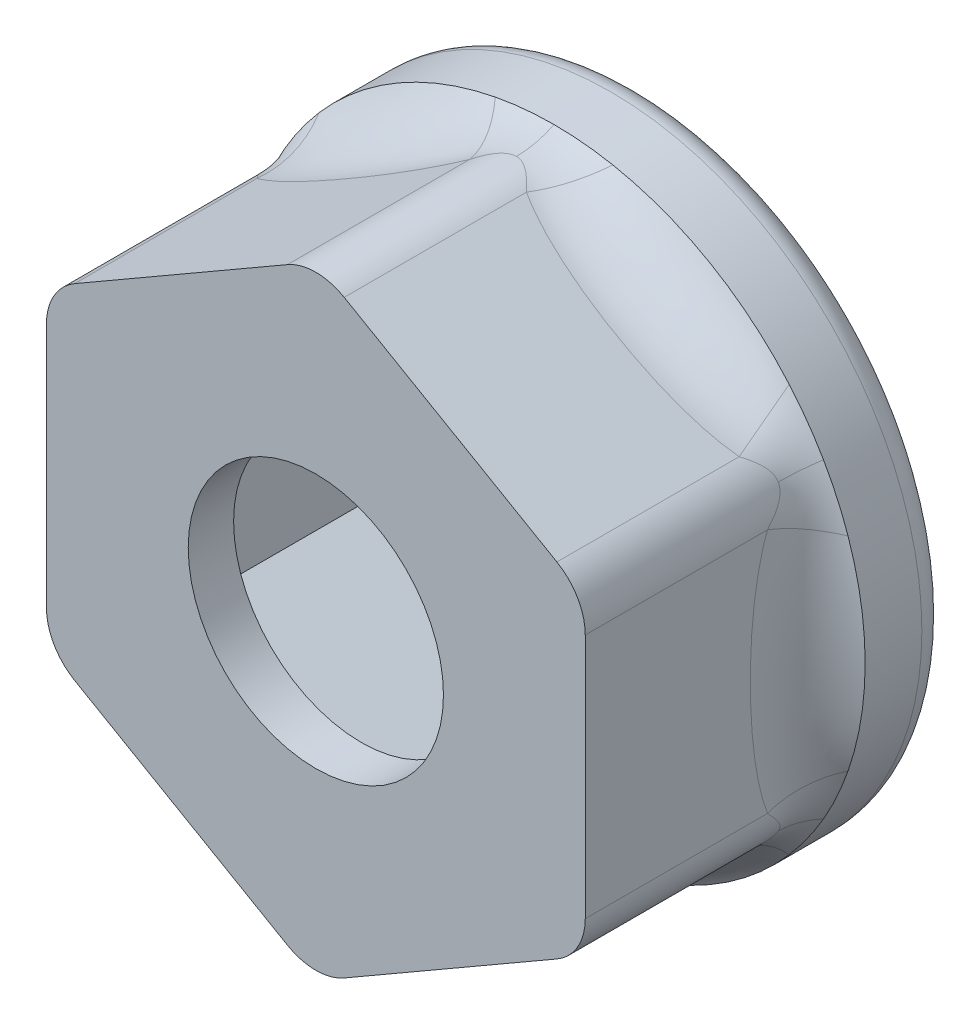
SolidWorks part; units mm, degrees
ref_plane "Front Plane" through (0, 0, 0) normal (0, 0, 1) x (1, 0, 0)
ref_plane "Top Plane" through (0, 0, 0) normal (0, 1, 0) x (1, 0, 0)
ref_plane "Right Plane" through (0, 0, 0) normal (1, 0, 0) x (0, 0, -1)
sketch "Sketch1" plane through (0, 0, 0) normal (0, 0, 1) x (1, 0, 0)
  line L1 (0, -7.5633) -> (6.55, -3.7816)
  line L2 (6.55, -3.7816) -> (6.55, 3.7816)
  line L3 (6.55, 3.7816) -> (0, 7.5633)
  line L4 (0, 7.5633) -> (-6.55, 3.7816)
  line L5 (-6.55, 3.7816) -> (-6.55, -3.7816)
  line L6 (-6.55, -3.7816) -> (0, -7.5633)
  line L7 (0, -10.9697) -> (9.5, -5.4848) construction
  line L8 (9.5, -5.4848) -> (9.5, 5.4848) construction
  line L9 (9.5, 5.4848) -> (0, 10.9697) construction
  line L10 (0, 10.9697) -> (-9.5, 5.4848) construction
  line L11 (-9.5, 5.4848) -> (-9.5, -5.4848) construction
  line L12 (-9.5, -5.4848) -> (0, -10.9697) construction
  circle A0 centre (0, 0) radius 6.55 construction
  circle A1 centre (0, 0) radius 10.9697
  circle A2 centre (0, 0) radius 9.5 construction
  point P1 (0, 0)
  point P18 (-1.0956, 10.9148)
  point P19 (0, 0)
  dimension "D1" = 13.1
  dimension "D2" = 19
extrude "Boss-Extrude1" add sketch "Sketch1" along normal blind 6.8
sketch "Sketch7" plane through (0, 0, 6.8) normal (0, 0, 1) x (1, 0, 0)
  circle A0 centre (0, 0) radius 4.5
  circle A1 centre (0, 0) radius 10.9697 construction
  circle A2 centre (0, 0) radius 10.9697
  dimension "D1" = 9
extrude "Boss-Extrude2" add sketch "Sketch7" along normal blind 1.6
sketch "Sketch9" plane through (0, 0, 0) normal (0, 0, -1) x (-1, 0, 0)
  circle A1 centre (0, 0) radius 10.9697 construction
  circle A2 centre (0, 0) radius 10.9697
extrude "Boss-Extrude3" add sketch "Sketch9" along normal blind 3
sketch "Sketch10" plane through (0, 0, 0) normal (0, 0, 1) x (1, 0, 0)
  line L1 (0, -10.9697) -> (9.5, -5.4848)
  line L2 (9.5, -5.4848) -> (9.5, 5.4848)
  line L3 (9.5, 5.4848) -> (0, 10.9697)
  line L4 (0, 10.9697) -> (-9.5, 5.4848)
  line L5 (-9.5, 5.4848) -> (-9.5, -5.4848)
  line L6 (-9.5, -5.4848) -> (0, -10.9697)
  circle A0 centre (0, 0) radius 9.5 construction
  circle A1 centre (0, 0) radius 10.9697 construction
  circle A2 centre (0, 0) radius 10.9697
extrude "Cut-Extrude2" cut sketch "Sketch10" along normal up to next (8.4 mm away) contours L5 A2 | L4 A2 | L3 A2 | L2 A2 | L1 A2 | L6 A2 region at (-5.0457, -8.7394, 0) region at (5.0457, -8.7394, 0) region at (10.0914, 0, 0) region at (-10.0914, 0, 0) region at (5.0457, 8.7394, 0) region at (-5.0457, 8.7394, 0) body kept at (9.5, -5.4848, 0)
fillet "Fillet6" radius 2 6 edges at (0, 10.9697, 4.2) (-9.5, 5.4848, 4.2) (-9.5, -5.4848, 4.2) (0, -10.9697, 4.2) (9.5, -5.4848, 4.2) (9.5, 5.4848, 4.2)
fillet "Fillet7" radius 3 6 edges at (9.5, 0, 0) (4.75, -8.2272, 0) (-4.75, -8.2272, 0) (-9.5, 0, 0) (-4.75, 8.2272, 0) (4.75, 8.2272, 0)
fillet "Fillet8" radius 1 1 edges at (-10.9697, 0, -3)
